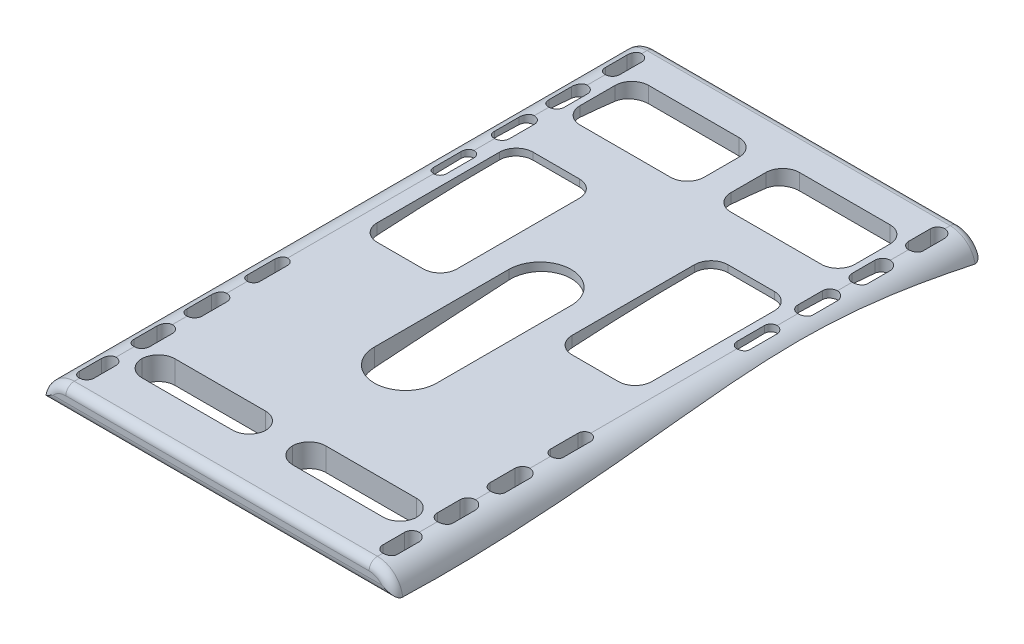
SolidWorks part; units mm, degrees
ref_plane "Front Plane" through (0, 0, 0) normal (0, 0, 1) x (1, 0, 0)
ref_plane "Top Plane" through (0, 0, 0) normal (0, 1, 0) x (1, 0, 0)
ref_plane "Right Plane" through (0, 0, 0) normal (1, 0, 0) x (0, 0, -1)
sketch "Sketch1" plane through (0, 0, 0) normal (0, 0, 1) x (1, 0, 0)
  line L0 (-90, 0) -> (90, 0)
  line L1 (-104.2804, -19.5903) -> (104.2804, -19.5903)
  arc A0 (90, 0) -> (104.2804, -19.5903) centre (90, -15) cw
  arc A1 (-90, 0) -> (-104.2804, -19.5903) centre (-90, -15) ccw
  point P3 (-102.2423, -23.6675)
  point P4 (0, 0)
  dimension "D2" = 15
  dimension "D3" = 15
  dimension "D1" = 180
extrude "Boss-Extrude3" add sketch "Sketch1" along normal blind 350
sketch "Sketch2" plane through (0, 0, 0) normal (1, 0, 0) x (0, 0, -1)
  line L0 (0, -19.5903) -> (0, 0) construction
  line L1 (-350, 0) -> (-350, -19.5903) construction
  line L2 (-350, -13.3374) -> (-350, -19.5903)
  line L3 (-350, -19.5903) -> (0, -19.5903)
  line L4 (0, -19.5903) -> (0, -13.3374)
  spline S0 degree 3 poles (0, -13.3374) (-116.2082, 9.851) (-233.2205, -18.1149) (-350, -13.3374) knots 0 0 0 0 1 1 1 1
  point P2 (0, 0)
  point P7 (0, 0)
extrude "Cut-Extrude1" cut sketch "Sketch2" against normal mid plane 350
sketch "Sketch3" plane through (0, 0, 0) normal (0, 1, 0) x (1, 0, 0)
  line L0 (0, 0) -> (0, -350) construction
  line L1 (90, 0) -> (-90, 0) construction
  line L2 (90, -350) -> (-90, -350) construction
  line L3 (0, -158.54) -> (0, -238.3291) construction
  line L4 (-81.5804, -22.3964) -> (-7.9289, -22.3964)
  line L5 (-81.5804, -22.3964) -> (-81.5804, -63.1279)
  line L6 (-81.5804, -63.1279) -> (-7.9289, -63.1279)
  line L7 (-7.9289, -22.3964) -> (-7.9289, -63.1279)
  line L8 (-81.5804, -91.0262) -> (-34.1533, -91.0262)
  line L9 (-81.5804, -91.0262) -> (-81.5804, -183.6485)
  line L10 (-81.5804, -183.6485) -> (-34.1533, -183.6485)
  line L11 (-34.1533, -91.0262) -> (-34.1533, -183.6485)
  line L12 (-81.5804, -303.5508) -> (-7.9289, -303.5508)
  line L13 (-81.5804, -303.5508) -> (-81.5804, -323.1569)
  line L14 (-81.5804, -323.1569) -> (-7.9289, -323.1569)
  line L15 (-7.9289, -303.5508) -> (-7.9289, -323.1569)
  line L16 (18.5303, -158.54) -> (18.5303, -238.3291)
  line L17 (-18.5303, -158.54) -> (-18.5303, -238.3291)
  line L18 (81.5804, -323.1569) -> (7.9289, -323.1569)
  line L19 (7.9289, -303.5508) -> (7.9289, -323.1569)
  line L20 (81.5804, -303.5508) -> (7.9289, -303.5508)
  line L21 (81.5804, -303.5508) -> (81.5804, -323.1569)
  line L22 (81.5804, -183.6485) -> (34.1533, -183.6485)
  line L23 (34.1533, -91.0262) -> (34.1533, -183.6485)
  line L24 (81.5804, -91.0262) -> (34.1533, -91.0262)
  line L25 (81.5804, -91.0262) -> (81.5804, -183.6485)
  line L26 (81.5804, -63.1279) -> (7.9289, -63.1279)
  line L27 (7.9289, -22.3964) -> (7.9289, -63.1279)
  line L28 (81.5804, -22.3964) -> (7.9289, -22.3964)
  line L29 (81.5804, -22.3964) -> (81.5804, -63.1279)
  line L30 (-90, -12.4558) -> (-90, -25.438) construction
  line L31 (-90, -350) -> (-90, 0) construction
  line L32 (-85.705, -12.4558) -> (-85.705, -25.438)
  line L33 (-94.295, -12.4558) -> (-94.295, -25.438)
  line L34 (-90, -45.1534) -> (-90, -58.6165) construction
  line L35 (-85.3994, -45.1534) -> (-85.3994, -58.6165)
  line L36 (-94.6006, -45.1534) -> (-94.6006, -58.6165)
  line L37 (-90, -76.4086) -> (-90, -91.0262) construction
  line L38 (-85.5292, -76.4086) -> (-85.5292, -91.0262)
  line L39 (-94.4708, -76.4086) -> (-94.4708, -91.0262)
  line L40 (-90, -111.5072) -> (-90, -127.8552) construction
  line L41 (-86.2155, -111.5072) -> (-86.2155, -127.8552)
  line L42 (-93.7845, -111.5072) -> (-93.7845, -127.8552)
  line L43 (0, -175) -> (-90, -175) construction
  line L44 (-90, -337.5442) -> (-90, -324.562) construction
  line L45 (-85.705, -337.5442) -> (-85.705, -324.562)
  line L46 (-94.295, -337.5442) -> (-94.295, -324.562)
  line L47 (-90, -304.8466) -> (-90, -291.3835) construction
  line L48 (-85.3994, -304.8466) -> (-85.3994, -291.3835)
  line L49 (-94.6006, -304.8466) -> (-94.6006, -291.3835)
  line L50 (-90, -273.5914) -> (-90, -258.9738) construction
  line L51 (-85.5292, -273.5914) -> (-85.5292, -258.9738)
  line L52 (-94.4708, -273.5914) -> (-94.4708, -258.9738)
  line L53 (-90, -238.4928) -> (-90, -222.1448) construction
  line L54 (-86.2155, -238.4928) -> (-86.2155, -222.1448)
  line L55 (-93.7845, -238.4928) -> (-93.7845, -222.1448)
  line L56 (90, -304.8466) -> (90, -291.3835) construction
  line L57 (85.3994, -304.8466) -> (85.3994, -291.3835)
  line L58 (94.6006, -304.8466) -> (94.6006, -291.3835)
  line L59 (90, -12.4558) -> (90, -25.438) construction
  line L60 (85.705, -12.4558) -> (85.705, -25.438)
  line L61 (94.295, -12.4558) -> (94.295, -25.438)
  line L62 (90, -45.1534) -> (90, -58.6165) construction
  line L63 (85.3994, -45.1534) -> (85.3994, -58.6165)
  line L64 (94.6006, -45.1534) -> (94.6006, -58.6165)
  line L65 (90, -76.4086) -> (90, -91.0262) construction
  line L66 (85.5292, -76.4086) -> (85.5292, -91.0262)
  line L67 (94.4708, -76.4086) -> (94.4708, -91.0262)
  line L68 (90, -111.5072) -> (90, -127.8552) construction
  line L69 (86.2155, -111.5072) -> (86.2155, -127.8552)
  line L70 (93.7845, -111.5072) -> (93.7845, -127.8552)
  line L71 (90, -238.4928) -> (90, -222.1448) construction
  line L72 (86.2155, -238.4928) -> (86.2155, -222.1448)
  line L73 (93.7845, -238.4928) -> (93.7845, -222.1448)
  line L74 (90, -273.5914) -> (90, -258.9738) construction
  line L75 (85.5292, -273.5914) -> (85.5292, -258.9738)
  line L76 (94.4708, -273.5914) -> (94.4708, -258.9738)
  line L77 (90, -337.5442) -> (90, -324.562) construction
  line L78 (85.705, -337.5442) -> (85.705, -324.562)
  line L79 (94.295, -337.5442) -> (94.295, -324.562)
  arc A0 (18.5303, -158.54) -> (-18.5303, -158.54) centre (0, -158.54) ccw
  arc A1 (-18.5303, -238.3291) -> (18.5303, -238.3291) centre (0, -238.3291) ccw
  arc A2 (-85.705, -12.4558) -> (-94.295, -12.4558) centre (-90, -12.4558) ccw
  arc A3 (-94.295, -25.438) -> (-85.705, -25.438) centre (-90, -25.438) ccw
  arc A4 (-85.3994, -45.1534) -> (-94.6006, -45.1534) centre (-90, -45.1534) ccw
  arc A5 (-94.6006, -58.6165) -> (-85.3994, -58.6165) centre (-90, -58.6165) ccw
  arc A6 (-85.5292, -76.4086) -> (-94.4708, -76.4086) centre (-90, -76.4086) ccw
  arc A7 (-94.4708, -91.0262) -> (-85.5292, -91.0262) centre (-90, -91.0262) ccw
  arc A8 (-86.2155, -111.5072) -> (-93.7845, -111.5072) centre (-90, -111.5072) ccw
  arc A9 (-93.7845, -127.8552) -> (-86.2155, -127.8552) centre (-90, -127.8552) ccw
  arc A10 (-85.705, -337.5442) -> (-94.295, -337.5442) centre (-90, -337.5442) cw
  arc A11 (-94.295, -324.562) -> (-85.705, -324.562) centre (-90, -324.562) cw
  arc A12 (-85.3994, -304.8466) -> (-94.6006, -304.8466) centre (-90, -304.8466) cw
  arc A13 (-94.6006, -291.3835) -> (-85.3994, -291.3835) centre (-90, -291.3835) cw
  arc A14 (-85.5292, -273.5914) -> (-94.4708, -273.5914) centre (-90, -273.5914) cw
  arc A15 (-94.4708, -258.9738) -> (-85.5292, -258.9738) centre (-90, -258.9738) cw
  arc A16 (-86.2155, -238.4928) -> (-93.7845, -238.4928) centre (-90, -238.4928) cw
  arc A17 (-93.7845, -222.1448) -> (-86.2155, -222.1448) centre (-90, -222.1448) cw
  arc A18 (85.3994, -304.8466) -> (94.6006, -304.8466) centre (90, -304.8466) ccw
  arc A19 (94.6006, -291.3835) -> (85.3994, -291.3835) centre (90, -291.3835) ccw
  arc A20 (85.705, -12.4558) -> (94.295, -12.4558) centre (90, -12.4558) cw
  arc A21 (94.295, -25.438) -> (85.705, -25.438) centre (90, -25.438) cw
  arc A22 (85.3994, -45.1534) -> (94.6006, -45.1534) centre (90, -45.1534) cw
  arc A23 (94.6006, -58.6165) -> (85.3994, -58.6165) centre (90, -58.6165) cw
  arc A24 (85.5292, -76.4086) -> (94.4708, -76.4086) centre (90, -76.4086) cw
  arc A25 (94.4708, -91.0262) -> (85.5292, -91.0262) centre (90, -91.0262) cw
  arc A26 (86.2155, -111.5072) -> (93.7845, -111.5072) centre (90, -111.5072) cw
  arc A27 (93.7845, -127.8552) -> (86.2155, -127.8552) centre (90, -127.8552) cw
  arc A28 (86.2155, -238.4928) -> (93.7845, -238.4928) centre (90, -238.4928) ccw
  arc A29 (93.7845, -222.1448) -> (86.2155, -222.1448) centre (90, -222.1448) ccw
  arc A30 (85.5292, -273.5914) -> (94.4708, -273.5914) centre (90, -273.5914) ccw
  arc A31 (94.4708, -258.9738) -> (85.5292, -258.9738) centre (90, -258.9738) ccw
  arc A32 (85.705, -337.5442) -> (94.295, -337.5442) centre (90, -337.5442) ccw
  arc A33 (94.295, -324.562) -> (85.705, -324.562) centre (90, -324.562) ccw
  point P20 (0, -198.4346)
  point P41 (-90, -18.9469)
  point P46 (-90, -51.885)
  point P53 (-90, -83.7174)
  point P60 (-90, -119.6812)
  point P69 (-86.2155, -119.6812)
  point P72 (-90, -331.0531)
  point P79 (-90, -298.115)
  point P86 (-90, -266.2826)
  point P93 (-90, -230.3188)
  point P98 (-86.2155, -230.3188)
  point P101 (90, -298.115)
  point P108 (90, -18.9469)
  point P115 (90, -51.885)
  point P122 (90, -83.7174)
  point P129 (90, -119.6812)
  point P136 (90, -230.3188)
  point P143 (90, -266.2826)
  point P150 (90, -331.0531)
extrude "Cut-Extrude2" cut sketch "Sketch3" against normal blind 40
fillet "Fillet1" radius 10 8 edges at (7.9289, -2.6396, 63.1279) (81.5804, -2.6396, 63.1279) (-7.9289, -2.6396, 63.1279) (-81.5804, -2.6396, 63.1279) (81.5804, -4.7405, 22.3964) (7.9289, -4.7405, 22.3964) (-7.9289, -4.7405, 22.3964) (-81.5804, -4.7405, 22.3964)
fillet "Fillet2" radius 10 8 edges at (-81.5804, -3.4902, 183.6485) (34.1533, -3.4902, 183.6485) (-34.1533, -3.4902, 183.6485) (81.5804, -3.4902, 183.6485) (81.5804, -2.0727, 91.0262) (34.1533, -2.0727, 91.0262) (-81.5804, -2.0727, 91.0262) (-34.1533, -2.0727, 91.0262)
fillet "Fillet3" radius 10 8 edges at (7.9289, -6.9483, 323.1569) (-81.5804, -6.9483, 323.1569) (7.9289, -6.8533, 303.5508) (-81.5804, -6.8533, 303.5508) (-7.9289, -6.9483, 323.1569) (81.5804, -6.9483, 323.1569) (81.5804, -6.8533, 303.5508) (-7.9289, -6.8533, 303.5508)
fillet "Fillet4" radius 5 4 edges at (100.0015, -3.821, 0) (-100.0015, -3.821, 0) (0, 0, 0) (0, -13.3374, 0)
fillet "Fillet5" radius 5 4 edges at (100.0015, -3.821, 350) (-100.0015, -3.821, 350) (0, -13.3374, 350) (0, 0, 350)
